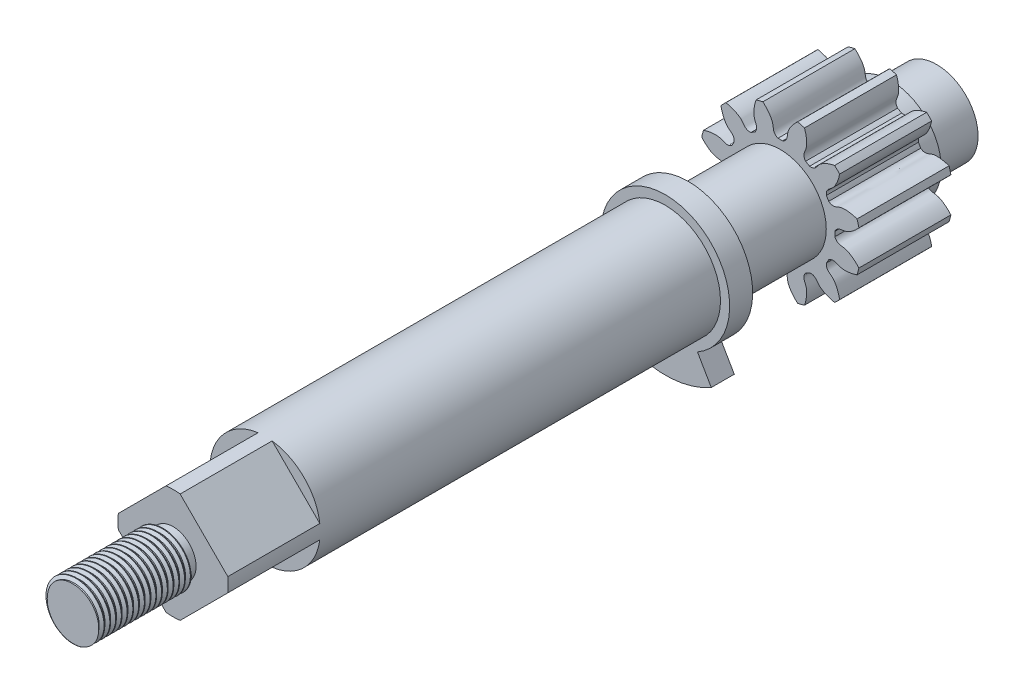
SolidWorks part; units mm, degrees
ref_plane "前视基准面" through (0, 0, 0) normal (0, 0, 1) x (1, 0, 0)
ref_plane "上视基准面" through (0, 0, 0) normal (0, 1, 0) x (1, 0, 0)
ref_plane "右视基准面" through (0, 0, 0) normal (1, 0, 0) x (0, 0, -1)
sketch "草图1" plane through (0, 0, 0) normal (0, 0, 1) x (1, 0, 0)
  circle A0 centre (0, 0) radius 17.5
extrude "凸台-拉伸1" add sketch "草图1" along normal blind 20
ref_axis "基准轴1" through (0, 0, -1) along (0, 0, 1)
sketch "草图2" plane through (0, 0, 0) normal (0, 0, 1) x (1, 0, 0)
  line L0 (0, 0) -> (0, 17.5) construction
  circle A0 centre (0, 0) radius 17.5 construction
  arc A1 (0.5021, 11.8644) -> (-0.5021, 11.8644) centre (0, 0) ccw
  arc A2 (8.744, 19.7374) -> (-8.744, 19.7374) centre (0, 0) ccw
  spline S0 degree 3 poles (0.5021, 11.8644) (1.702, 12.3733) (1.4359, 13.362) (1.6904, 14.2237) (1.7066, 14.2748) (1.7256, 14.3308) (1.7476, 14.3918) (1.7729, 14.4576) (1.8016, 14.5281) (1.8339, 14.6032) (1.8701, 14.6828) (1.9103, 14.7667) (1.9547, 14.8548) (2.0035, 14.947) (2.0568, 15.0431) (2.1149, 15.143) (2.1779, 15.2466) (2.246, 15.3537) (2.3194, 15.464) (2.3981, 15.5775) (2.4824, 15.694) (2.5724, 15.8132) (2.6683, 15.9351) (2.7702, 16.0594) (2.8781, 16.1859) (2.9924, 16.3145) (3.113, 16.4448) (3.2401, 16.5768) (3.3738, 16.7102) (3.5142, 16.8449) (3.6615, 16.9805) (3.8156, 17.1168) (3.9768, 17.2537) (4.145, 17.391) (4.3203, 17.5283) (4.5029, 17.6654) (4.6927, 17.8022) (4.8899, 17.9384) (5.0945, 18.0737) (5.3065, 18.2079) (5.526, 18.3407) (5.753, 18.472) (5.9875, 18.6014) (6.2295, 18.7287) (6.479, 18.8537) (6.7361, 18.9761) (7.0007, 19.0956) (7.2729, 19.2121) (7.5525, 19.3252) (7.8397, 19.4347) (8.2359, 19.5768) (8.539, 19.6753) (8.744, 19.7374) knots 0 0 0 0 0.218015 0.222044 0.226546 0.231522 0.236972 0.242897 0.249295 0.256167 0.263513 0.271332 0.279626 0.288394 0.297636 0.307351 0.317541 0.328204 0.339341 0.350953 0.363038 0.375597 0.38863 0.402137 0.416118 0.430573 0.445502 0.460904 0.476781 0.493132 0.509956 0.527255 0.545027 0.563273 0.581994 0.601188 0.620856 0.640998 0.661614 0.682704 0.704268 0.726305 0.748817 0.771803 0.795262 0.819196 0.843603 0.868484 0.89384 0.919669 0.945972 1 1 1 1
  spline S1 degree 3 poles (-0.5021, 11.8644) (-1.702, 12.3733) (-1.4359, 13.362) (-1.6904, 14.2237) (-1.7066, 14.2748) (-1.7256, 14.3308) (-1.7476, 14.3918) (-1.7729, 14.4576) (-1.8016, 14.5281) (-1.8339, 14.6032) (-1.8701, 14.6828) (-1.9103, 14.7667) (-1.9547, 14.8548) (-2.0035, 14.947) (-2.0568, 15.0431) (-2.1149, 15.143) (-2.1779, 15.2466) (-2.246, 15.3537) (-2.3194, 15.464) (-2.3981, 15.5775) (-2.4824, 15.694) (-2.5724, 15.8132) (-2.6683, 15.9351) (-2.7702, 16.0594) (-2.8781, 16.1859) (-2.9924, 16.3145) (-3.113, 16.4448) (-3.2401, 16.5768) (-3.3738, 16.7102) (-3.5142, 16.8449) (-3.6615, 16.9805) (-3.8156, 17.1168) (-3.9768, 17.2537) (-4.145, 17.391) (-4.3203, 17.5283) (-4.5029, 17.6654) (-4.6927, 17.8022) (-4.8899, 17.9384) (-5.0945, 18.0737) (-5.3065, 18.2079) (-5.526, 18.3407) (-5.753, 18.472) (-5.9875, 18.6014) (-6.2295, 18.7287) (-6.479, 18.8537) (-6.7361, 18.9761) (-7.0007, 19.0956) (-7.2729, 19.2121) (-7.5525, 19.3252) (-7.8397, 19.4347) (-8.2359, 19.5768) (-8.539, 19.6753) (-8.744, 19.7374) knots 0 0 0 0 0.218015 0.222044 0.226546 0.231522 0.236972 0.242897 0.249295 0.256167 0.263513 0.271332 0.279626 0.288394 0.297636 0.307351 0.317541 0.328204 0.339341 0.350953 0.363038 0.375597 0.38863 0.402137 0.416118 0.430573 0.445502 0.460904 0.476781 0.493132 0.509956 0.527255 0.545027 0.563273 0.581994 0.601188 0.620856 0.640998 0.661614 0.682704 0.704268 0.726305 0.748817 0.771803 0.795262 0.819196 0.843603 0.868484 0.89384 0.919669 0.945972 1 1 1 1
extrude "切除-拉伸1" cut sketch "草图2" along normal through all
pattern_circular "阵列(圆周)1" count 12 every 30 about axis through (0, 0, -1) along (0, 0, 1) of "切除-拉伸1"
sketch "草图3" plane through (0, 0, 0) normal (0, 0, 1) x (1, 0, 0)
  circle A0 centre (0, 0) radius 15 construction
  dimension "Dn" = 30
sketch "草图5" plane through (0, 0, 0) normal (0, 0, -1) x (-1, 0, 0)
  circle A0 centre (0, 0) radius 11
  dimension "D1" = 22
extrude "凸台-拉伸2" add sketch "草图5" along normal blind 4
sketch "草图6" plane through (0, 0, -4) normal (0, 0, -1) x (-1, 0, 0)
  circle A0 centre (0, 0) radius 9
  dimension "D1" = 18
extrude "凸台-拉伸3" add sketch "草图6" along normal blind 10
sketch "草图7" plane through (0, 0, 20) normal (0, 0, 1) x (1, 0, 0)
  circle A0 centre (0, 0) radius 10
  dimension "D1" = 20
extrude "凸台-拉伸4" add sketch "草图7" along normal blind 20
sketch "草图8" plane through (0, 0, 40) normal (0, 0, 1) x (1, 0, 0)
  line L0 (0, 0) -> (-10, -17.3205) construction
  line L1 (0, -20) -> (0, 0) construction
  line L2 (0, 0) -> (10, -17.3205) construction
  line L3 (7, -12.1244) -> (10, -17.3205)
  line L4 (-7, -12.1244) -> (-10, -17.3205)
  arc A0 (-10, -17.3205) -> (10, -17.3205) centre (0, 0) ccw
  circle A1 centre (0, 0) radius 14
  circle M7 centre (0, 0) radius 10
  dimension "D1" = 40
  dimension "D2" = 28
  dimension "D3" = 60
extrude "凸台-拉伸5" add sketch "草图8" along normal blind 5 contours M7 | A1 M7 | A1 L4 A0 L3 region at (0, -16.4023, 40) region at (0, -13.604, 40) region at (0, 0, 40)
sketch "草图9" plane through (0, 0, 45) normal (0, 0, 1) x (1, 0, 0)
  circle A0 centre (0, 0) radius 12
  dimension "D1" = 24
extrude "凸台-拉伸6" add sketch "草图9" along normal blind 87
sketch "草图10" plane through (0, 0, 132) normal (0, 0, 1) x (1, 0, 0)
  circle A1 centre (0, 0) radius 12
  circle A2 centre (0, 0) radius 12
  dimension "D1" = 0
extrude "凸台-拉伸7" add sketch "草图10" along normal blind 20
sketch "草图11" plane through (0, 0, 152) normal (0, 0, 1) x (1, 0, 0)
  line L0 (-0.7071, 12.7279) -> (-12.7279, 0.7071)
  line L1 (0.7071, 12.7279) -> (12.7279, 0.7071)
  line L2 (-12.7279, -0.7071) -> (-0.7071, -12.7279)
  line L3 (12.7279, -0.7071) -> (0.7071, -12.7279)
  line L4 (13.435, 0) -> (-13.435, 0)
  line L5 (0, 13.435) -> (0, -13.435)
  line L6 (-0.7071, 12.7279) -> (0.7071, 12.7279)
  line L7 (12.7279, 0.7071) -> (12.7279, -0.7071)
  line L8 (-0.7071, -12.7279) -> (0.7071, -12.7279)
  line L9 (-12.7279, 0.7071) -> (-12.7279, -0.7071)
  circle A3 centre (0, 0) radius 12
  circle A4 centre (0, 0) radius 12
  circle M11 centre (0, 0) radius 12
  dimension "D1" = 19
  dimension "D2" = 19
  dimension "D3" = 0
extrude "切除-拉伸4" cut sketch "草图11" against normal blind 20 contours L1 M11 | L0 M11 | L3 M11 | L2 M11 region at (-7.4313, 7.4313, 152) region at (7.4313, 7.4313, 152) region at (-7.4313, -7.4313, 152) region at (7.4313, -7.4313, 152)
sketch "草图12" plane through (0, 0, 152) normal (0, 0, 1) x (1, 0, 0)
  circle A0 centre (0, 0) radius 5
  dimension "D1" = 10
extrude "凸台-拉伸8" add sketch "草图12" along normal blind 2
sketch "草图13" plane through (0, 0, 154) normal (0, 0, 1) x (1, 0, 0)
  circle A0 centre (0, 0) radius 6
  dimension "D1" = 12
extrude "凸台-拉伸9" add sketch "草图13" along normal blind 20
thread "螺纹线1" pitch 1.25 method cut profile "螺纹线轮廓1" start angle 0, offset 1, length 0, pitch 1.25, diameter 12
ref_plane "基准面1" through (6, 0, 153) normal (0, -1, 0) x (1, 0, 0)
sketch "螺纹线轮廓1" plane through (6, 0, 153) normal (0, -1, 0) x (1, 0, 0)
  line L0 (0, 0) -> (0, 1.25) construction
  line L11 (0, 0) -> (0, 1.0937)
  line L12 (0, 1.0937) -> (-0.6766, 0.7031)
  line L13 (-0.6766, 0.7031) -> (-0.6766, 0.3906)
  line L15 (-0.6766, 0.3906) -> (0, 0)
  line L17 (-0.6766, 0.5469) -> (0, 0.5469) construction
  point P2 (0, 0)
  dimension "Pitch" = 1.25
  dimension "Profile_Angle" = 60
  dimension "Profile_Land" = 0.3125
  dimension "Profile_Height" = 0.6766
